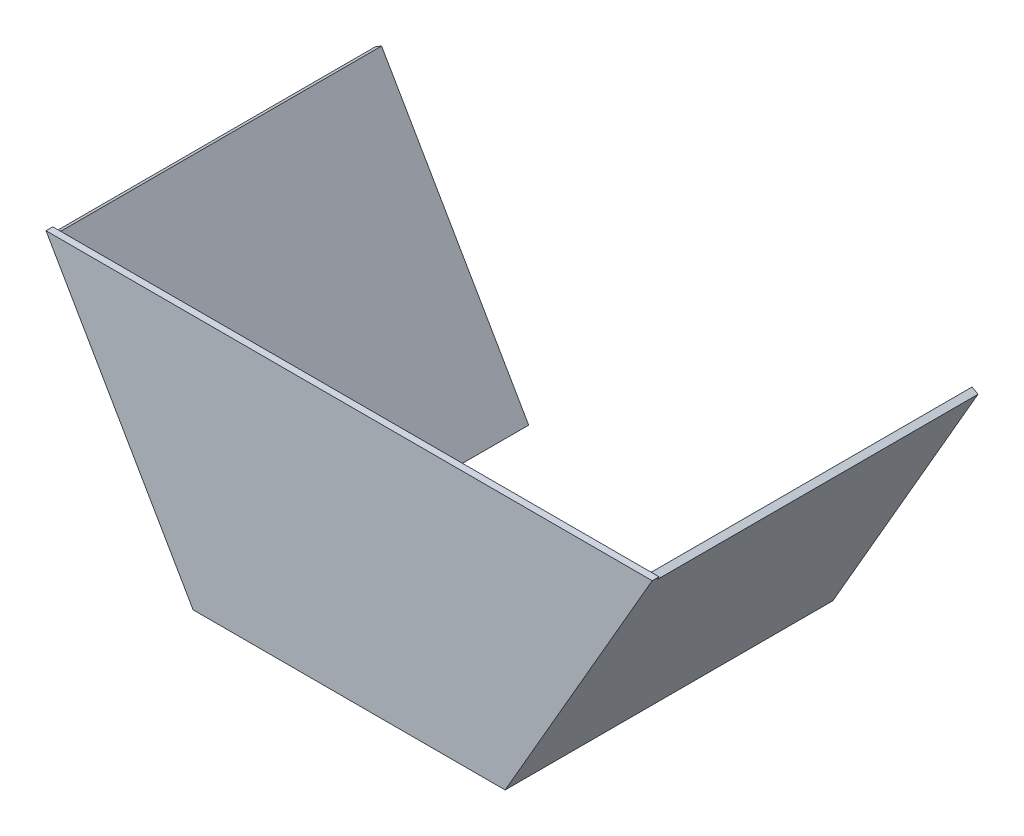
SolidWorks part; units mm, degrees
ref_plane "Front Plane" through (0, 0, 0) normal (0, 0, 1) x (1, 0, 0)
ref_plane "Top Plane" through (0, 0, 0) normal (0, 1, 0) x (1, 0, 0)
ref_plane "Right Plane" through (0, 0, 0) normal (1, 0, 0) x (0, 0, -1)
sketch "Sketch1" plane through (0, 0, 0) normal (0, 0, 1) x (1, 0, 0)
  line L0 (-138.5, 0) -> (138.5, 0) construction
  line L1 (-138.5, 0) -> (-276, 238.157)
  line L2 (138.5, 0) -> (276, 238.157)
  line L3 (-138.5, 0) -> (-145.8323, 0)
  line L4 (-145.8323, 0) -> (-281.4993, 234.982)
  line L5 (-281.4993, 234.982) -> (-276, 238.157)
  line L6 (138.5, 0) -> (145.8323, 0)
  line L7 (145.8323, 0) -> (281.4993, 234.982)
  line L8 (281.4993, 234.982) -> (276, 238.157)
  point P4 (0, 0)
  dimension "D1" = 60
  dimension "D2" = 60
  dimension "D3" = 277
  dimension "D4" = 275
  dimension "D5" = 275
  dimension "D6" = 6.35
  dimension "D7" = 6.35
extrude "Boss-Extrude1" add sketch "Sketch1" along normal blind 300
sketch "Sketch2" plane through (0, 0, 300) normal (0, 0, 1) x (1, 0, 0)
  line L0 (-145.8323, 0) -> (-283.3323, 238.157)
  line L1 (-283.3323, 238.157) -> (283.3323, 238.157)
  line L2 (283.3323, 238.157) -> (145.8323, 0)
  line L3 (145.8323, 0) -> (-145.8323, 0)
  line L4 (-281.4993, 234.982) -> (-145.8323, 0) construction
  line L5 (145.8323, 0) -> (281.4993, 234.982) construction
extrude "Boss-Extrude2" add sketch "Sketch2" along normal blind 6.35
sketch "Sketch3" plane through (0, 0, 0) normal (1, 0, 0) x (0, 0, -1)
  line L0 (168.4925, 0) -> (-168.4925, 0) construction
  line L1 (-300, 238.157) -> (-300, 0) construction
  circle A0 centre (-162.5, 137.5) radius 137.5 construction
  dimension "D1" = 275
